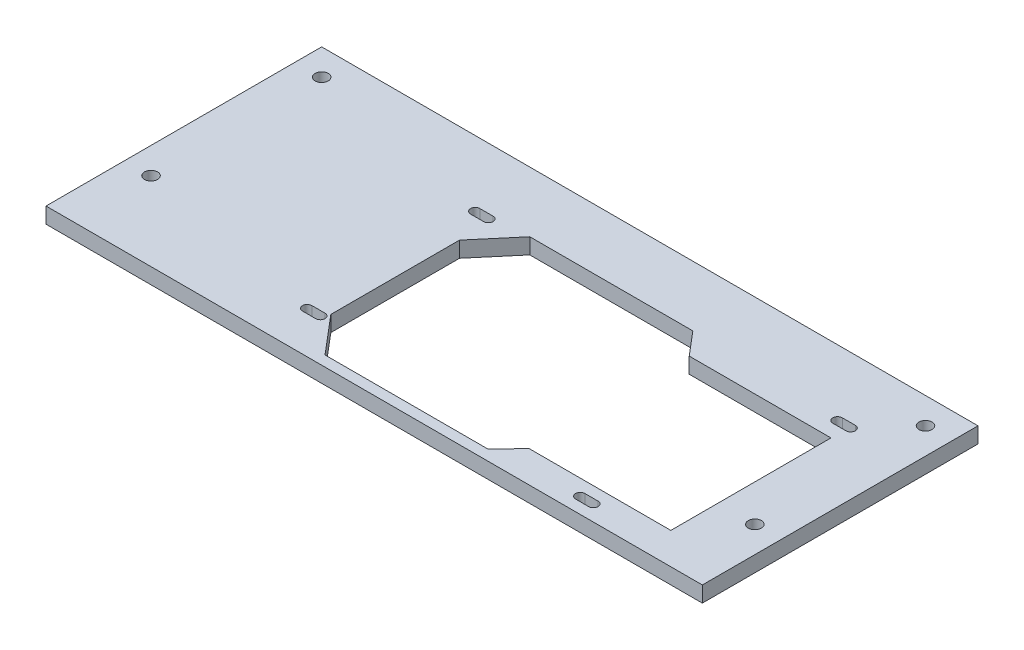
SolidWorks part; units mm, degrees
ref_plane "Front Plane" through (0, 0, 0) normal (0, 0, 1) x (1, 0, 0)
ref_plane "Top Plane" through (0, 0, 0) normal (0, 1, 0) x (1, 0, 0)
ref_plane "Right Plane" through (0, 0, 0) normal (1, 0, 0) x (0, 0, -1)
sketch "Sketch1" plane through (0, 0, 0) normal (0, 1, 0) x (1, 0, 0)
  line L0 (-22.7284, 29.5) -> (39.3832, 29.5)
  line L1 (-125, -52.5) -> (125, -52.5)
  line L2 (-125, -52.5) -> (-125, 52.5)
  line L3 (-125, 52.5) -> (125, 52.5)
  line L4 (125, -52.5) -> (125, 52.5)
  line L5 (-125, -52.5) -> (125, 52.5) construction
  line L6 (-125, 52.5) -> (125, -52.5) construction
  line L7 (39.3832, 29.5) -> (47, 20.5)
  line L8 (47, 20.5) -> (101, 20.5)
  line L9 (101, 20.5) -> (101, -40.5)
  line L10 (39.3832, -48.5) -> (-22.7284, -48.5)
  line L11 (-108.2019, -45.7879) -> (108.2019, 45.7879) construction
  line L12 (-108.2019, 45.7879) -> (108.2019, -45.7879) construction
  line L13 (-22.7284, -48.5) -> (-35, -34)
  line L14 (-35, -34) -> (-35, 15)
  line L15 (-35, 15) -> (-22.7284, 29.5)
  line L16 (101, -40.5) -> (47, -40.5)
  line L17 (47, -40.5) -> (39.3832, -48.5)
  line L18 (105, 32.5) -> (105, -52.5) construction
  line L19 (105, 32.5) -> (-125, 32.5) construction
  line L20 (-45, 32.5) -> (-45, -52.5) construction
  line L21 (72.5, -44.7) -> (77.5, -44.7)
  line L22 (72.5, -48.3) -> (77.5, -48.3)
  line L25 (96.5, 29.3) -> (101.5, 29.3)
  line L26 (96.5, 25.7) -> (101.5, 25.7)
  line L27 (96.5, 29.3) -> (101.5, 25.7) construction
  line L28 (101.5, 29.3) -> (96.5, 25.7) construction
  line L29 (-41.5, 29.3) -> (-36.5, 29.3)
  line L30 (-41.5, 25.7) -> (-36.5, 25.7)
  line L31 (-41.5, 29.3) -> (-36.5, 25.7) construction
  line L32 (-36.5, 29.3) -> (-41.5, 25.7) construction
  line L33 (-41.5, -34.7) -> (-36.5, -34.7)
  line L34 (-41.5, -38.3) -> (-36.5, -38.3)
  line L35 (-41.5, -34.7) -> (-36.5, -38.3) construction
  line L36 (-36.5, -34.7) -> (-41.5, -38.3) construction
  circle A0 centre (-115, -22.5) radius 2.5
  circle A1 centre (-115, 42.5) radius 2.5
  circle A2 centre (115, 42.5) radius 2.5
  circle A3 centre (115, -22.5) radius 2.5
  arc A4 (77.5, -44.7) -> (77.5, -48.3) centre (77.5, -46.5) cw
  arc A5 (72.5, -44.7) -> (72.5, -48.3) centre (72.5, -46.5) ccw
  arc A6 (101.5, 29.3) -> (101.5, 25.7) centre (101.5, 27.5) cw
  arc A7 (96.5, 29.3) -> (96.5, 25.7) centre (96.5, 27.5) ccw
  arc A8 (-36.5, 29.3) -> (-36.5, 25.7) centre (-36.5, 27.5) cw
  arc A9 (-41.5, 29.3) -> (-41.5, 25.7) centre (-41.5, 27.5) ccw
  arc A10 (-36.5, -34.7) -> (-36.5, -38.3) centre (-36.5, -36.5) cw
  arc A11 (-41.5, -34.7) -> (-41.5, -38.3) centre (-41.5, -36.5) ccw
  point P0 (0, 0)
  point P14 (0, 0)
  point P58 (75, -48.3)
  point P59 (-39, -38.3)
  point P60 (-39, 29.3)
  point P61 (99, 29.3)
  dimension "D5" = 5
  dimension "D1" = 250
  dimension "D2" = 105
  dimension "D3" = 10
  dimension "D4" = 30
  dimension "D6" = 10
  dimension "D7" = 10
  dimension "D8" = 78
  dimension "D9" = 4
  dimension "D10" = 136
  dimension "D11" = 24
  dimension "D12" = 54
  dimension "D13" = 61
  dimension "D14" = 139.758
  dimension "D15" = 20
  dimension "D16" = 20
  dimension "D17" = 12
  dimension "D18" = 49
  dimension "D19" = 150
  dimension "D20" = 3.6
  dimension "D21" = 5
  dimension "D22" = 3.6
  dimension "D23" = 5
  dimension "D24" = 3.6
  dimension "D25" = 5
  dimension "D26" = 3.6
  dimension "D27" = 5
  dimension "D28" = 6
  dimension "D29" = 30
  dimension "D30" = 16
  dimension "D31" = 6
  dimension "D32" = 64
  dimension "D33" = 138
  dimension "D34" = 6
  dimension "D35" = 74
extrude "Boss-Extrude1" add sketch "Sketch1" along normal blind 6 contours L3 L4 L1 L2
extrude "Cut-Extrude1" cut sketch "Sketch1<4>" along normal blind 6 contours A0 | A1 | A2 | A3 | L14 L15 L0 L7 L8 L9 L16 L17 L10 L13 | A10 L34 A11 L33 | A8 L30 A9 L29 | A6 L26 A7 L25 | A4 L22 A5 L21
sketch "Sketch1<4>" plane through (0, 0, 0) normal (0, 1, 0) x (1, 0, 0) same geometry as "Sketch1"
